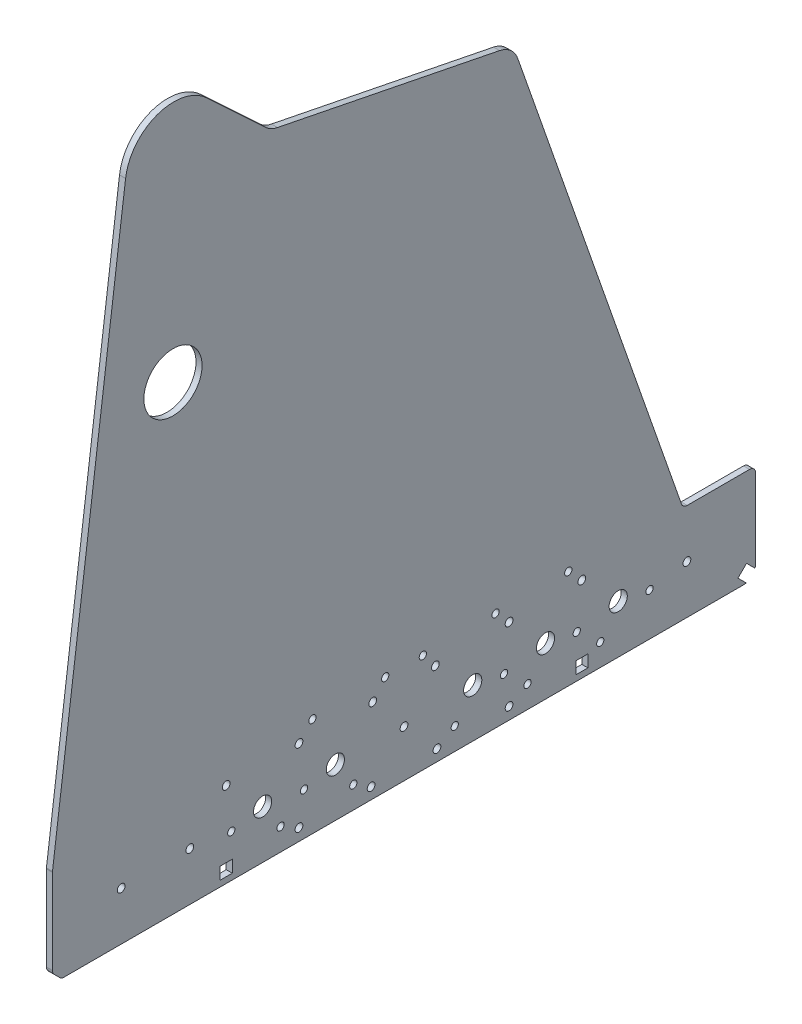
SolidWorks part; units mm, degrees
ref_plane "Front Plane" through (0, 0, 0) normal (0, 0, 1) x (1, 0, 0)
ref_plane "Top Plane" through (0, 0, 0) normal (0, 1, 0) x (1, 0, 0)
ref_plane "Right Plane" through (0, 0, 0) normal (1, 0, 0) x (0, 0, -1)
sketch "Sketch1" plane through (0, 0, 0) normal (1, 0, 0) x (0, 0, -1)
  line L0 (-184.15, -24.6062) -> (184.15, -24.6062)
  line L1 (184.15, -24.6062) -> (184.15, 26.1938)
  line L2 (184.15, 26.1938) -> (146.05, 26.1937)
  line L3 (146.05, 26.1937) -> (57.15, 280.1938)
  line L5 (-145.839, 321.5609) -> (-184.15, 26.1938)
  line L6 (-184.15, 26.1938) -> (-184.15, -24.6062)
  line L7 (-184.15, 350.0437) -> (184.15, 350.0437) construction
  line L8 (57.15, 280.1938) -> (-69.85, 305.5938)
  line L9 (-69.85, 305.5938) -> (-103.3099, 336.854)
  arc A0 (-103.3099, 336.854) -> (-145.839, 321.5609) centre (-120.65, 318.2937) ccw
  point P8 (0, -24.6062)
  dimension "D1" = 368.3
  dimension "D7" = 25.4
  dimension "D2" = 50.8
  dimension "D3" = 38.1
  dimension "D4" = 24.6062
  dimension "D5" = 374.65
  dimension "D6" = 304.8
  dimension "D8" = 342.9
  dimension "D9" = 127
  dimension "D10" = 304.8
  dimension "D11" = 25.4
  dimension "D12" = 127
extrude "Boss-Extrude1" add sketch "Sketch1" along normal blind 3.175
chamfer "Chamfer1" distance 4.7625 angle 45 2 edges at (1.5875, -24.6062, 184.15) (1.5875, -24.6062, -184.15)
fillet "Fillet1" radius 12.7 2 edges at (1.5875, 305.5938, 69.85) (1.5875, 280.1938, -57.15)
fillet "Fillet2" radius 3.175 3 edges at (1.5875, 26.1938, 184.15) (1.5875, 26.1938, -184.15) (1.5875, 26.1937, -146.05)
fillet "Fillet3" radius 3.175 4 edges at (1.5875, -19.8438, -184.15) (1.5875, -24.6062, -179.3875) (1.5875, -19.8437, 184.15) (1.5875, -24.6062, 179.3875)
sketch "Sketch16" plane through (3.175, 0, 0) normal (1, 0, 0) x (0, 0, -1)
  circle A0 centre (112.1746, 0.7937) radius 4.7625
  circle A1 centre (74.0746, 0.7937) radius 4.7625
  circle A2 centre (35.9746, 0.7937) radius 4.7625
  circle A3 centre (-35.9746, 0.7938) radius 4.7625
  circle A4 centre (-74.0746, 0.7938) radius 4.7625
  dimension "D1" = 9.525
extrude "Cut-Extrude1" cut sketch "Sketch16" against normal up to next
sketch "Sketch25" plane through (3.175, 0, 0) normal (1, 0, 0) x (0, 0, -1)
  circle A0 centre (102.7672, -13.0003) radius 1.905 construction
  circle A1 centre (86.0486, 27.3622) radius 1.905 construction
  circle A2 centre (128.5804, -2.3081) radius 1.905 construction
  circle A3 centre (102.7672, -13.0003) radius 1.905
  circle A4 centre (86.0486, 27.3622) radius 1.905
  circle A5 centre (128.5804, -2.3081) radius 1.905
  circle A6 centre (64.6672, -13.0003) radius 1.905 construction
  circle A8 centre (-9.8486, 27.3622) radius 1.905 construction
  circle A10 centre (-47.9486, 27.3622) radius 1.905 construction
  circle A11 centre (-90.4804, -2.3081) radius 1.905 construction
  circle A12 centre (-64.6672, -13.0003) radius 1.905 construction
  circle A14 centre (-52.3804, -2.3081) radius 1.905 construction
  circle A15 centre (-26.5672, -13.0003) radius 1.905 construction
  circle A16 centre (9.8486, 27.3622) radius 1.905 construction
  circle A17 centre (26.5672, -13.0003) radius 1.905 construction
  circle A18 centre (47.9486, 27.3622) radius 1.905 construction
  circle A19 centre (52.3804, -2.3081) radius 1.905 construction
  circle A20 centre (90.4804, -2.3081) radius 1.905 construction
  circle A21 centre (-9.8486, 27.3622) radius 1.905
  circle A23 centre (-47.9486, 27.3622) radius 1.905
  circle A24 centre (-90.4804, -2.3081) radius 1.905
  circle A25 centre (-64.6672, -13.0003) radius 1.905
  circle A27 centre (-52.3804, -2.3081) radius 1.905
  circle A28 centre (-26.5672, -13.0003) radius 1.905
  circle A29 centre (9.8486, 27.3622) radius 1.905
  circle A30 centre (26.5672, -13.0003) radius 1.905
  circle A31 centre (47.9486, 27.3622) radius 1.905
  circle A32 centre (64.6672, -13.0003) radius 1.905
  circle A33 centre (52.3804, -2.3081) radius 1.905
  circle A34 centre (90.4804, -2.3081) radius 1.905
extrude "Cut-Extrude4" cut sketch "Sketch25" against normal up to next
sketch "Sketch23" plane through (3.175, 0, 0) normal (1, 0, 0) x (0, 0, -1)
  point P0 (-55.0246, -18.3223)
  point P3 (-55.0246, 19.9098)
  point P6 (-93.1246, 19.9098)
  point P9 (-17.2515, -18.6426)
  point P12 (-16.4124, 19.3854)
  point P15 (16.4124, 19.3854)
  point P18 (17.2515, -18.6426)
  point P21 (55.0246, -18.3223)
  point P27 (93.1246, 19.9098)
  point P30 (55.0246, 19.9098)
hole_wizard "#8 (0.16) Diameter Hole1" positions "Sketch23" profile "Sketch24" hole size "#8" standard "ANSI Inch" end condition up to next
sketch "Sketch24" plane through (3.175, -18.3223, 55.0246) normal (0, 1, 0) x (0, 0, -1)
  line L0 (0, 0) -> (0, 3.175)
  line L1 (0, 3.175) -> (2.032, 3.175)
  line L2 (2.032, 3.175) -> (2.032, 0)
  line L5 (2.032, 0) -> (0, 0)
  line L11 (0, -6.35) -> (0, 107.95) construction
  dimension "Thru Hole Dia." = 4.064
  dimension "Thru Hole Depth" = 3.175
sketch "Sketch22" plane through (3.175, 0, 0) normal (1, 0, 0) x (0, 0, -1)
  line L0 (-96.2996, -15.1473) -> (-89.9496, -15.1473) construction
  line L1 (-96.2996, -15.1473) -> (-89.9496, -15.1473)
  line L2 (-96.2996, -15.1473) -> (-96.2996, -21.4973)
  line L3 (-96.2996, -21.4973) -> (-89.9496, -21.4973)
  line L4 (-89.9496, -15.1473) -> (-89.9496, -21.4973)
  line L5 (-96.2996, -15.1473) -> (-89.9496, -21.4973) construction
  line L6 (-96.2996, -21.4973) -> (-89.9496, -15.1473) construction
  line L7 (-89.9496, -15.1473) -> (-89.9496, -19.8734) construction
  line L77 (179.3875, -24.6062) -> (183.8776, -20.1161)
  line L78 (179.3875, -24.6062) -> (174.8974, -20.1161)
  line L79 (183.8776, -20.1161) -> (179.3875, -15.626)
  line L80 (174.8974, -20.1161) -> (179.3875, -15.626)
  line L81 (180.3174, -23.6763) -> (183.2201, -20.7737) construction
  line L82 (-178.0724, -24.6062) -> (178.0724, -24.6062) construction
  line L84 (89.9496, -21.4973) -> (96.2996, -21.4973)
  line L85 (89.9496, -21.4973) -> (89.9496, -15.1473)
  line L86 (89.9496, -15.1473) -> (96.2996, -15.1473)
  line L87 (96.2996, -21.4973) -> (96.2996, -15.1473)
  line L88 (89.9496, -21.4973) -> (96.2996, -15.1473) construction
  line L89 (89.9496, -15.1473) -> (96.2996, -21.4973) construction
  point P0 (-93.1246, -18.3223)
  point P19 (93.1246, -18.3223)
  dimension "D1" = 6.35
  dimension "D2" = 6.35
extrude "Cut-Extrude3" cut sketch "Sketch22" against normal up to next
sketch "Sketch21" plane through (3.175, 0, 0) normal (1, 0, 0) x (0, 0, -1)
  circle A0 centre (-148.1579, 0.7937) radius 2.032
  circle A1 centre (-112.1746, 0.7937) radius 2.032
  circle A2 centre (0, 0) radius 2.032
  circle A3 centre (148.1579, 0.7938) radius 2.032
  dimension "D1" = 4.064
extrude "Cut-Extrude2" cut sketch "Sketch21" against normal up to next
sketch "Sketch26" plane through (3.175, 0, 0) normal (1, 0, 0) x (0, 0, -1)
  line L0 (-145.839, 321.5609) -> (-184.1236, 26.3971) construction
  line L1 (-178.0724, -24.6062) -> (178.0724, -24.6062) construction
  circle A0 centre (-121.0218, 216.6937) radius 15.24
  dimension "D1" = 30.48
  dimension "D2" = 38.1
  dimension "D3" = 241.3
extrude "Cut-Extrude5" cut sketch "Sketch26" against normal through all
